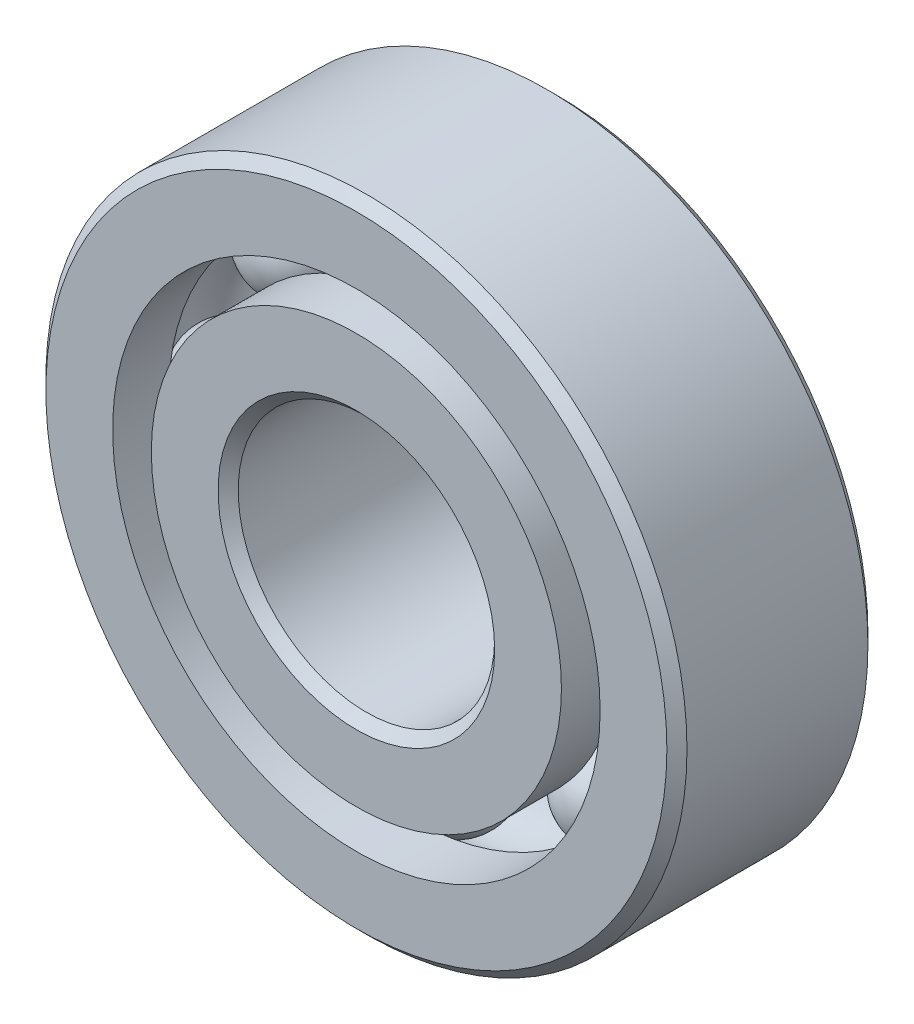
SolidWorks part; units mm, degrees
ref_plane "Front Plane" through (0, 0, 0) normal (0, 0, 1) x (1, 0, 0)
ref_plane "Top Plane" through (0, 0, 0) normal (0, 1, 0) x (1, 0, 0)
ref_plane "Right Plane" through (0, 0, 0) normal (1, 0, 0) x (0, 0, -1)
sketch "Sketch1" plane through (0, 0, 0) normal (1, 0, 0) x (0, 0, -1)
  line L0 (-2.4892, 0) -> (2.4892, 0) construction
  line L1 (0, 7.9375) -> (0, -7.9375) construction
  line L2 (2.2403, 7.9375) -> (-2.2403, 7.9375)
  line L3 (-2.2403, 7.9375) -> (-2.4892, 7.6886)
  line L4 (-2.4892, 7.6886) -> (-2.4892, 6.0352)
  line L5 (-2.4892, 6.0352) -> (-1.1063, 6.0352)
  line L6 (2.4892, 6.0352) -> (1.1063, 6.0352)
  line L7 (2.4892, 7.6886) -> (2.4892, 6.0352)
  line L8 (2.2403, 7.9375) -> (2.4892, 7.6886)
  line L9 (0, 7.9375) -> (0, 5.5562) construction
  line L10 (0, 5.5562) -> (0, 3.175) construction
  arc A0 (-1.1063, 6.0352) -> (1.1063, 6.0352) centre (0, 5.5562) cw
  point P14 (0, 3.175)
  dimension "D3" = 2.2126
  dimension "D1" = 45
  dimension "Width" = 4.9784
  dimension "OD" = 15.875
  dimension "D2" = 0.2489
  dimension "Shaft Dia" = 6.35
  dimension "D4" = 0.479
revolve "Revolve1" add sketch "Sketch1" angle 360 about L0
sketch "Sketch3" plane through (0, 0, 0) normal (1, 0, 0) x (0, 0, -1)
  line L0 (-2.4892, 5.0773) -> (-1.1063, 5.0773)
  line L1 (0, 7.9375) -> (0, -7.9375) construction
  line L2 (-2.4892, 7.6886) -> (-2.4892, 6.0352) construction
  line L3 (-2.4892, 5.0773) -> (-2.4892, 3.4239)
  line L4 (-2.2403, 7.9375) -> (-2.4892, 7.6886) construction
  line L5 (-2.4892, 3.4239) -> (-2.2403, 3.175)
  line L6 (-2.2403, 3.175) -> (2.2403, 3.175)
  line L7 (2.2403, 7.9375) -> (2.2403, -7.9375) construction
  line L8 (2.2403, 3.175) -> (2.4892, 3.4239)
  line L9 (2.4892, -7.6886) -> (2.4892, 7.6886) construction
  line L10 (2.4892, 3.4239) -> (2.4892, 5.0773)
  line L11 (2.4892, 5.0773) -> (1.1063, 5.0773)
  line L13 (2.2403, 7.9375) -> (2.4892, 7.6886) construction
  arc A0 (1.1063, 6.0352) -> (-1.1063, 6.0352) centre (0, 5.5562) ccw construction
  arc A1 (1.1063, 5.0773) -> (-1.1063, 5.0773) centre (0, 5.5562) cw
revolve "Revolve3" add sketch "Sketch3" angle 360 about L0
sketch "Sketch4" plane through (0, 0, 0) normal (1, 0, 0) x (0, 0, -1)
  line L0 (-1.2055, 5.5562) -> (1.2055, 5.5562)
  arc A2 (-1.2055, 5.5562) -> (1.2055, 5.5562) centre (0, 5.5562) cw
  arc A3 (1.1063, 6.0352) -> (-1.1063, 6.0352) centre (0, 5.5562) ccw construction
revolve "Revolve4" add sketch "Sketch4" angle 360 about L0
ref_axis "Axis1" through (0, 0, -2.4892) along (0, 0, 1)
pattern_circular "CirPattern1" count 8 every 45 about axis through (0, 0, -2.4892) along (0, 0, 1) of bodies 104
sketch "Sketch5" plane through (0, 0, 0) normal (1, 0, 0) x (0, 0, -1)
  line L0 (-2.4892, 6.0352) -> (-1.1063, 6.0352) construction
  line L1 (-2.3647, 6.0352) -> (-1.2055, 6.0352)
  line L2 (-2.3647, 6.0352) -> (-2.3647, 5.0773)
  line L3 (-2.3647, 5.0773) -> (-1.2055, 5.0773)
  line L4 (-1.2055, 6.0352) -> (-1.2055, 5.0773)
  line L5 (-2.4892, 5.0773) -> (-1.1063, 5.0773) construction
  line L6 (2.4892, 6.0352) -> (1.1063, 6.0352) construction
  line L7 (2.3647, 6.0352) -> (1.2055, 6.0352)
  line L8 (2.3647, 6.0352) -> (2.3647, 5.0773)
  line L9 (2.3647, 5.0773) -> (1.2055, 5.0773)
  line L10 (1.2055, 6.0352) -> (1.2055, 5.0773)
  line L11 (2.4892, 5.0773) -> (1.1063, 5.0773) construction
  line L12 (-2.2403, 7.9375) -> (-2.4892, 7.6886) construction
  point P18 (-2.3647, 7.813)
revolve "Revolve5" [suppressed] add sketch "Sketch5" angle 360 about L0
equation "\"D2@Sketch1\" = \"Width@Sketch1\"*.05"
equation "\"D3@Sketch1\" = \"Width@Sketch1\"/2.25"
equation "\"D4@Sketch1\" = (((\"OD@Sketch1\"-\"Width@Sketch1\")/2)/3.25)/3.5"
equation "\"D2@CirPattern1\" = 360/\"Balls@CirPattern1\""
